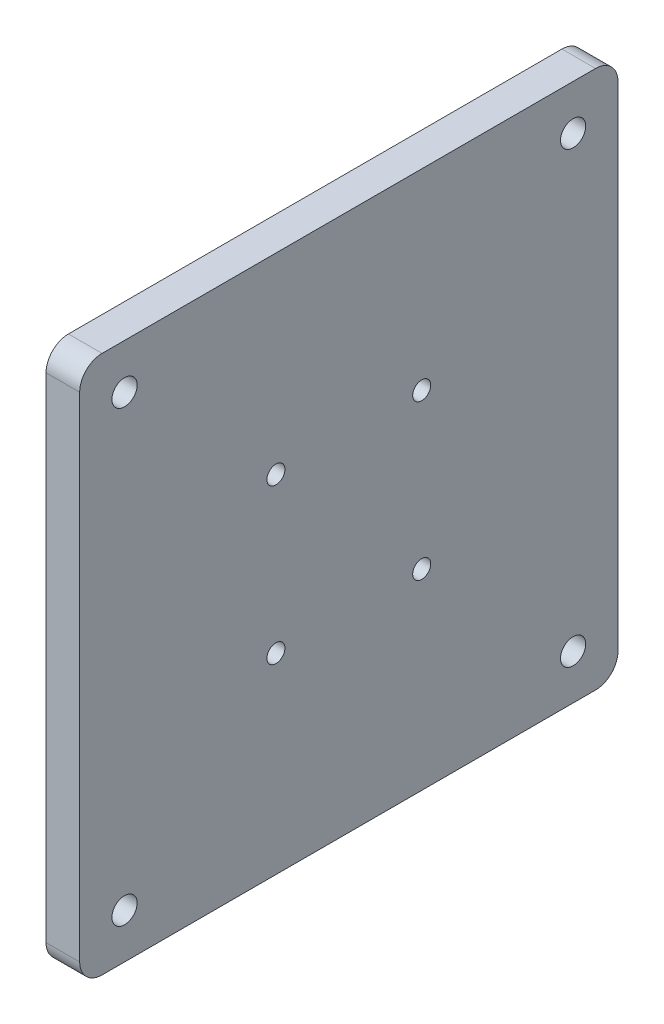
SolidWorks part; units mm, degrees
ref_plane "Front Plane" through (0, 0, 0) normal (0, 0, 1) x (1, 0, 0)
ref_plane "Top Plane" through (0, 0, 0) normal (0, 1, 0) x (1, 0, 0)
ref_plane "Right Plane" through (0, 0, 0) normal (1, 0, 0) x (0, 0, -1)
sketch "Sketch1" plane through (0, 0, 0) normal (1, 0, 0) x (0, 0, -1)
  line L1 (-76.2, -76.2) -> (76.2, -76.2)
  line L2 (-76.2, -76.2) -> (-76.2, 76.2)
  line L3 (-76.2, 76.2) -> (76.2, 76.2)
  line L4 (76.2, -76.2) -> (76.2, 76.2)
  line L5 (-76.2, -76.2) -> (76.2, 76.2) construction
  line L6 (-76.2, 76.2) -> (76.2, -76.2) construction
  point P0 (0, 0)
  point P5 (0, 0)
  dimension "D1" = 152.4
  dimension "D2" = 152.4
extrude "Boss-Extrude1" add sketch "Sketch1" along normal blind 9.525
hole_wizard "1/4-20 Tapped Hole1" positions "Sketch2" profile "Sketch3" tap size "1/4-20" standard "ANSI Inch" end condition through all
sketch "Sketch2" plane through (9.525, 0, 0) normal (1, 0, 0) x (0, 0, -1)
  line L1 (-20.6375, -21.9075) -> (20.6375, -21.9075) construction
  line L2 (-20.6375, -21.9075) -> (-20.6375, 21.9075) construction
  line L3 (-20.6375, 21.9075) -> (20.6375, 21.9075) construction
  line L4 (20.6375, -21.9075) -> (20.6375, 21.9075) construction
  line L5 (-20.6375, -21.9075) -> (20.6375, 21.9075) construction
  line L6 (-20.6375, 21.9075) -> (20.6375, -21.9075) construction
  point P0 (-20.6375, 21.9075)
  point P58 (20.6375, 21.9075)
  point P61 (20.6375, -21.9075)
  point P64 (-20.6375, -21.9075)
  dimension "D1" = 43.815
  dimension "D2" = 41.275
cosmetic thread "Hole Thread1" parameters "D2"=6.35
cosmetic thread "Hole Thread2" parameters "D2"=6.35
cosmetic thread "Hole Thread3" parameters "D2"=6.35
cosmetic thread "Hole Thread4" parameters "D2"=6.35
sketch "Sketch3" plane through (9.525, 21.9075, 20.6375) normal (0, 1, 0) x (0, 0, -1)
  line L0 (0, 0) -> (0, 9.525)
  line L1 (0, 9.525) -> (2.5527, 9.525)
  line L2 (2.5527, 9.525) -> (2.5527, 0)
  line L5 (2.5527, 0) -> (0, 0)
  line L11 (0, -6.35) -> (0, 107.95) construction
  dimension "Thru Tap Drill Dia." = 5.1054
  dimension "Thru Tap Drill Depth" = 9.525
sketch "Sketch4" plane through (9.525, 0, 0) normal (1, 0, 0) x (0, 0, -1)
  line L5 (19.05, 29.972) -> (19.05, 76.2) construction
  line L6 (76.2, 76.2) -> (-76.2, 76.2) construction
  line L7 (0, -76.2) -> (0, 76.2) construction
  line L8 (-29.972, 29.972) -> (29.972, 29.972) construction
  line L9 (-29.972, 29.972) -> (-29.972, -29.972) construction
  line L10 (-29.972, -29.972) -> (29.972, -29.972) construction
  line L11 (29.972, 29.972) -> (29.972, -29.972) construction
  line L12 (-29.972, 29.972) -> (29.972, -29.972) construction
  line L13 (-29.972, -29.972) -> (29.972, 29.972) construction
  line L14 (-76.2, -76.2) -> (76.2, -76.2) construction
  line L15 (-76.2, 0) -> (76.2, 0) construction
  line L16 (15.875, 49.022) -> (22.225, 49.022) construction
  line L17 (15.875, 49.022) -> (15.875, 35.052)
  line L18 (15.875, 35.052) -> (22.225, 35.052) construction
  line L19 (22.225, 49.022) -> (22.225, 35.052)
  line L20 (15.875, 49.022) -> (22.225, 35.052) construction
  line L21 (15.875, 35.052) -> (22.225, 49.022) construction
  line L22 (-76.2, 76.2) -> (-76.2, -76.2) construction
  line L23 (76.2, -76.2) -> (76.2, 76.2) construction
  line L24 (-15.875, 35.052) -> (-22.225, 49.022) construction
  line L25 (-15.875, 49.022) -> (-22.225, 35.052) construction
  line L26 (-15.875, 35.052) -> (-22.225, 35.052) construction
  line L27 (-15.875, 49.022) -> (-22.225, 49.022) construction
  line L28 (-22.225, 49.022) -> (-22.225, 35.052)
  line L29 (-15.875, 49.022) -> (-15.875, 35.052)
  line L30 (-15.875, -49.022) -> (-22.225, -49.022) construction
  line L31 (-15.875, -35.052) -> (-22.225, -35.052) construction
  line L32 (-15.875, -49.022) -> (-22.225, -35.052) construction
  line L33 (-15.875, -35.052) -> (-22.225, -49.022) construction
  line L34 (15.875, -35.052) -> (22.225, -49.022) construction
  line L35 (15.875, -49.022) -> (22.225, -35.052) construction
  line L36 (15.875, -35.052) -> (22.225, -35.052) construction
  line L37 (15.875, -49.022) -> (22.225, -49.022) construction
  line L38 (-15.875, -49.022) -> (-15.875, -35.052)
  line L39 (-22.225, -49.022) -> (-22.225, -35.052)
  line L40 (22.225, -49.022) -> (22.225, -35.052)
  line L41 (15.875, -49.022) -> (15.875, -35.052)
  line L42 (11.0908, 31.877) -> (29.972, 31.877) construction
  arc A0 (15.875, 49.022) -> (22.225, 49.022) centre (19.05, 49.022) cw
  arc A1 (22.225, 35.052) -> (15.875, 35.052) centre (19.05, 35.052) cw
  arc A2 (-22.225, 35.052) -> (-15.875, 35.052) centre (-19.05, 35.052) ccw
  arc A3 (-15.875, 49.022) -> (-22.225, 49.022) centre (-19.05, 49.022) ccw
  arc A4 (-15.875, -49.022) -> (-22.225, -49.022) centre (-19.05, -49.022) cw
  arc A5 (-22.225, -35.052) -> (-15.875, -35.052) centre (-19.05, -35.052) cw
  arc A6 (22.225, -35.052) -> (15.875, -35.052) centre (19.05, -35.052) ccw
  arc A7 (15.875, -49.022) -> (22.225, -49.022) centre (19.05, -49.022) ccw
  point P7 (0, 0)
  point P13 (19.05, 42.037)
  point P33 (-19.05, 42.037)
  point P46 (-19.05, -42.037)
  point P47 (19.05, -42.037)
  dimension "D4" = 19.05
  dimension "D1" = 13.97
  dimension "D2" = 59.944
  dimension "D3" = 6.35
  dimension "D5" = 1.905
ref_axis "Axis1" through (0, 0, 0) along (1, 0, 0)
fillet "Fillet1" radius 6.35 4 edges at (4.7625, -76.2, 76.2) (4.7625, -76.2, -76.2) (4.7625, 76.2, -76.2) (4.7625, 76.2, 76.2)
hole_wizard "1/4 Clearance Hole1" positions "Sketch5" profile "Sketch6" hole size "1/4" standard "ANSI Inch" end condition through all
sketch "Sketch5" plane through (9.525, 0, 0) normal (1, 0, 0) x (0, 0, -1)
  line L0 (-76.2, 69.85) -> (-76.2, -69.85) construction
  line L1 (69.85, 76.2) -> (-69.85, 76.2) construction
  line L2 (-76.2, 0) -> (76.2, 0) construction
  line L4 (0, -76.2) -> (0, 76.2) construction
  point P0 (-63.5, 63.5)
  point P17 (63.5, 63.5)
  point P18 (63.5, -63.5)
  point P19 (-63.5, -63.5)
  dimension "D1" = 12.7
  dimension "D2" = 12.7
sketch "Sketch6" plane through (9.525, 63.5, 63.5) normal (0, 1, 0) x (0, 0, -1)
  line L0 (0, 0) -> (0, 9.525)
  line L1 (0, 9.525) -> (3.5712, 9.525)
  line L2 (3.5712, 9.525) -> (3.5712, 0)
  line L5 (3.5712, 0) -> (0, 0)
  line L11 (0, -6.35) -> (0, 107.95) construction
  dimension "Thru Hole Dia." = 7.1425
  dimension "Thru Hole Depth" = 9.525
